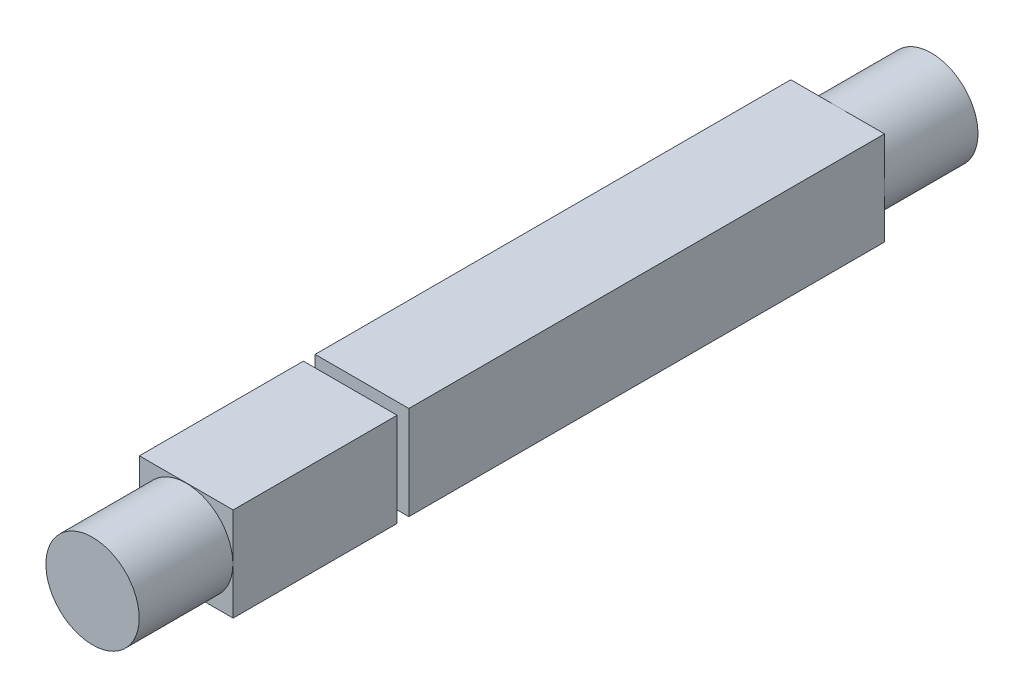
SolidWorks part; units mm, degrees
ref_plane "Front Plane" through (0, 0, 0) normal (0, 0, 1) x (1, 0, 0)
ref_plane "Top Plane" through (0, 0, 0) normal (0, 1, 0) x (1, 0, 0)
ref_plane "Right Plane" through (0, 0, 0) normal (1, 0, 0) x (0, 0, -1)
sketch "Sketch1" plane through (0, 0, 0) normal (0, 0, 1) x (1, 0, 0)
  line L1 (2, -2) -> (-2, -2)
  line L2 (2, -2) -> (2, 2)
  line L3 (2, 2) -> (-2, 2)
  line L4 (-2, -2) -> (-2, 2)
  line L5 (2, -2) -> (-2, 2) construction
  line L6 (2, 2) -> (-2, -2) construction
  dimension "D2" = 4
extrude "Boss-Extrude1" add sketch "Sketch1" along normal mid plane 27.8
sketch "Sketch2" plane through (0, 0, 13.9) normal (0, 0, 1) x (1, 0, 0)
  circle A0 centre (0, 0) radius 1.99
  dimension "D1" = 3.98
extrude "Boss-Extrude2" add sketch "Sketch2" along normal blind 4
mirror "Mirror2" about plane through (0, 0, 0) normal (0, 0, 1) of "Boss-Extrude2"
sketch "Sketch3" plane through (0, 2, 0) normal (0, 1, 0) x (1, 0, 0)
  line L0 (-2, -13.9) -> (-2, 13.9) construction
  line L1 (-2, -6.9) -> (2, -6.9)
  line L2 (-2, -6.9) -> (-2, -6.4)
  line L3 (-2, -6.4) -> (2, -6.4)
  line L4 (2, -6.9) -> (2, -6.4)
  line L5 (2, -13.9) -> (2, 13.9) construction
  line L7 (2, -13.9) -> (-2, -13.9) construction
  dimension "D1" = 0.5
  dimension "D2" = 7
extrude "Cut-Extrude1" cut sketch "Sketch3" against normal up to next
